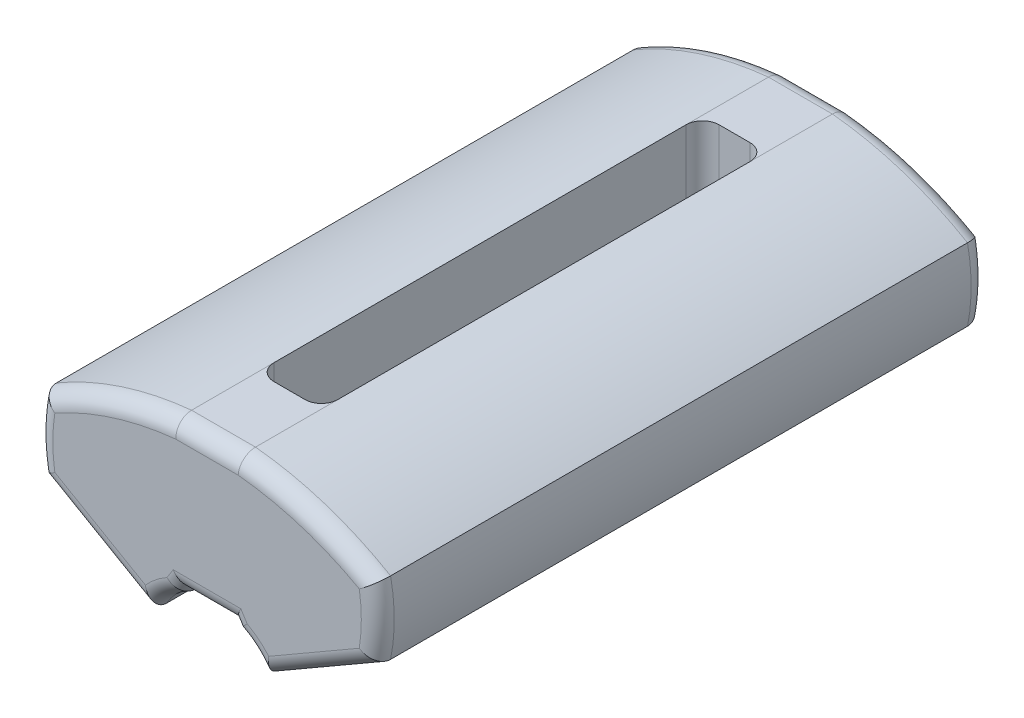
SolidWorks part; units mm, degrees
material "Медь"
ref_plane "Спереди" through (0, 0, 0) normal (0, 0, 1) x (1, 0, 0)
ref_plane "Сверху" through (0, 0, 0) normal (0, 1, 0) x (1, 0, 0)
ref_plane "Справа" through (0, 0, 0) normal (1, 0, 0) x (0, 0, -1)
sketch "Эскиз1" plane through (0, 0, 0) normal (0, 0, 1) x (1, 0, 0)
  line L0 (0, 0) -> (0, 7.5) construction
  line L1 (-6, 4.5) -> (6, 4.5) construction
  line L2 (-0.75, 6.2538) -> (-0.75, 1.9843) construction
  line L3 (0.75, 6.2538) -> (0.75, 1.9843) construction
  line L4 (5.791, -2.4774) -> (2.0935, -0.3426) construction
  line L5 (5.041, -3.7764) -> (1.3435, -1.6417) construction
  line L6 (6.8971, 2.9462) -> (0.8971, -7.4462) construction
  line L7 (-5.041, -3.7764) -> (-1.3435, -1.6417) construction
  line L8 (-5.791, -2.4774) -> (-2.0935, -0.3426) construction
  line L9 (-0.8971, -7.4462) -> (-6.8971, 2.9462) construction
  arc A0 (5.2489, 5.3571) -> (-5.2489, 5.3571) centre (0, 0) ccw construction
  circle A1 centre (0, 0) radius 1 construction
  arc A2 (-0.75, 6.4566) -> (0.75, 6.4566) centre (0, 0) ccw construction
  arc A3 (-5.0679, 5.1207) -> (-0.9694, 6.4529) centre (0, -3.5) cw construction
  circle A4 centre (0, 0) radius 7.5 construction
  arc A5 (5.2489, 5.3571) -> (5.0679, 5.1207) centre (5.1439, 5.25) cw construction
  arc A6 (-5.0679, 5.1207) -> (-5.2489, 5.3571) centre (-5.1439, 5.25) cw construction
  arc A7 (-0.8636, 1.8039) -> (-1.9941, -0.154) centre (0, 0) ccw construction
  arc A8 (0.9694, 6.4529) -> (5.0679, 5.1207) centre (0, -3.5) cw construction
  circle A9 centre (0, 0) radius 6.5 construction
  arc A10 (0.9694, 6.4529) -> (0.75, 6.2538) centre (0.95, 6.2538) ccw construction
  arc A11 (0.75, 1.9843) -> (0.8636, 1.8039) centre (0.95, 1.9843) ccw construction
  arc A12 (-0.75, 1.9843) -> (-0.8636, 1.8039) centre (-0.95, 1.9843) cw construction
  arc A13 (-0.75, 6.2538) -> (-0.9694, 6.4529) centre (-0.95, 6.2538) ccw construction
  arc A14 (2.015, -7.2243) -> (7.2639, 1.8671) centre (0, 0) ccw construction
  arc A15 (6.9686, 1.8286) -> (6.0731, -2.3869) centre (-3.0311, 1.75) cw construction
  arc A16 (2.015, -7.2243) -> (1.9007, -6.9493) centre (1.9747, -7.0798) cw construction
  arc A17 (6.9686, 1.8286) -> (7.2639, 1.8671) centre (7.1186, 1.8298) cw construction
  arc A18 (5.1037, -4.066) -> (1.9007, -6.9493) centre (-3.0311, 1.75) cw construction
  arc A19 (5.1037, -4.066) -> (5.041, -3.7764) centre (4.941, -3.9496) ccw construction
  arc A20 (1.3435, -1.6417) -> (1.1304, -1.6499) centre (1.2435, -1.8149) ccw construction
  arc A21 (2.0935, -0.3426) -> (1.9941, -0.154) centre (2.1935, -0.1694) cw construction
  arc A22 (5.791, -2.4774) -> (6.0731, -2.3869) centre (5.891, -2.3042) ccw construction
  arc A23 (-7.2639, 1.8671) -> (-2.015, -7.2243) centre (0, 0) ccw construction
  arc A24 (-1.9007, -6.9493) -> (-5.1037, -4.066) centre (3.0311, 1.75) cw construction
  arc A25 (-7.2639, 1.8671) -> (-6.9686, 1.8286) centre (-7.1186, 1.8298) cw construction
  arc A26 (-1.9007, -6.9493) -> (-2.015, -7.2243) centre (-1.9747, -7.0798) cw construction
  arc A27 (-6.0731, -2.3869) -> (-6.9686, 1.8286) centre (3.0311, 1.75) cw construction
  arc A28 (-6.0731, -2.3869) -> (-5.791, -2.4774) centre (-5.891, -2.3042) ccw construction
  arc A29 (-2.0935, -0.3426) -> (-1.9941, -0.154) centre (-2.1935, -0.1694) ccw construction
  arc A30 (-1.3435, -1.6417) -> (-1.1304, -1.6499) centre (-1.2435, -1.8149) cw construction
  arc A31 (-5.041, -3.7764) -> (-5.1037, -4.066) centre (-4.941, -3.9496) ccw construction
  arc A32 (1.9941, -0.154) -> (0.8636, 1.8039) centre (0, 0) ccw construction
  arc A33 (-1.1304, -1.6499) -> (1.1304, -1.6499) centre (0, 0) ccw construction
  point P24 (0.75, 6.4718)
  point P27 (0.75, 1.854)
  point P30 (-0.75, 1.854)
  point P33 (-0.75, 6.4718)
  point P78 (0, 0)
  dimension "D1" = 15
  dimension "D2" = 2
  dimension "D5" = 0.15
  dimension "D6" = 4
  dimension "D8" = 0.2
  dimension "D4" = 12
  dimension "D7" = 0.75
  dimension "D3" = 1
  dimension "D9" = 3
sketch "Эскиз2" plane through (0, 0, 0) normal (0, 0, 1) x (1, 0, 0)
  line L4 (0, 7.5) -> (0, 0) construction
  line L5 (-5.0679, 2.926) -> (-1.7321, 1)
  line L7 (-0.8636, 1.8039) -> (-0.75, 1.9843)
  line L12 (0.8636, 1.8039) -> (0.75, 1.9843)
  line L13 (5.0679, 2.926) -> (1.7321, 1)
  line L14 (-0.75, 1.9843) -> (0.75, 1.9843)
  line L15 (-0.9694, 6.4529) -> (0.9694, 6.4529)
  arc A0 (-5.0679, 5.1207) -> (-5.0679, 2.926) centre (0.3092, 4.0233) ccw
  arc A1 (-5.0679, 5.1207) -> (-0.9694, 6.4529) centre (0, -3.5) cw
  arc A2 (-0.8636, 1.8039) -> (-1.7321, 1) centre (0, 0) ccw
  arc A3 (0.8636, 1.8039) -> (1.7321, 1) centre (0, 0) cw
  arc A4 (5.0679, 5.1207) -> (0.9694, 6.4529) centre (0, -3.5) ccw
  arc A5 (5.0679, 5.1207) -> (5.0679, 2.926) centre (-0.3092, 4.0233) cw
extrude "Бобышка-Вытянуть1" add sketch "Эскиз2" along normal blind 18.5
fillet "Скругление1" radius 0.5 24 edges at (0.8068, 1.8941, 18.5) (0, 1.9843, 18.5) (-0.8068, 1.8941, 18.5) (-1.3587, 1.4677, 18.5) (-3.4, 1.963, 18.5) (-5.1787, 4.0233, 18.5) (-3.0913, 6.0102, 18.5) (0, 6.4529, 18.5) (3.0913, 6.0102, 18.5) (5.1787, 4.0233, 18.5) (3.4, 1.963, 18.5) (1.3587, 1.4677, 18.5) (3.4, 1.963, 0) (5.1787, 4.0233, 0) (3.0913, 6.0102, 0) (0, 6.4529, 0) (-3.0913, 6.0102, 0) (-5.1787, 4.0233, 0) (-3.4, 1.963, 0) (-1.3587, 1.4677, 0) (-0.8068, 1.8941, 0) (0, 1.9843, 0) (0.8068, 1.8941, 0) (1.3587, 1.4677, 0)
sketch "Эскиз3" plane through (0, 6.4529, 0) normal (0, 1, 0) x (1, 0, 0)
  line L0 (-0.9694, -2.5) -> (-0.9694, -16)
  line L1 (-0.9694, -2.5) -> (0.9694, -2.5)
  line L2 (-0.9694, -16) -> (0.9694, -16)
  line L3 (0.9694, -2.5) -> (0.9694, -16)
  line L4 (-0.9694, -18) -> (-0.9694, -0.5) construction
  line L5 (0.9694, -18) -> (0.9694, -0.5) construction
  line L6 (-5.0679, -9.25) -> (5.1787, -9.25) construction
  line L7 (-5.0679, -18) -> (-5.0679, -0.5) construction
  line L8 (5.1787, -18) -> (5.1787, -0.5) construction
  dimension "D1" = 13.5
  dimension "D2" = 6.75
extrude "Вырез-Вытянуть1" cut sketch "Эскиз3" against normal blind 18.5
fillet "Скругление2" radius 0.5 4 edges at (-0.9694, 4.1011, 16) (0.9694, 4.1011, 16) (-0.9694, 4.1011, 2.5) (0.9694, 4.1011, 2.5)
